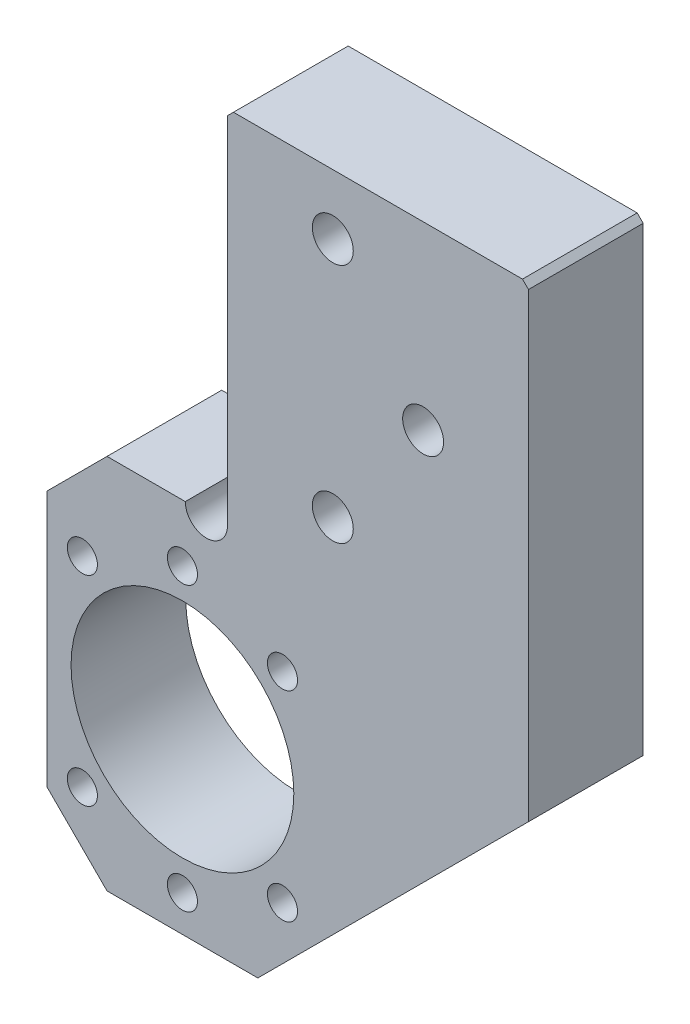
SolidWorks part; units mm, degrees
material "6061-T6 (SS)"
ref_plane "Front Plane" through (0, 0, 0) normal (0, 0, 1) x (1, 0, 0)
ref_plane "Top Plane" through (0, 0, 0) normal (0, 1, 0) x (1, 0, 0)
ref_plane "Right Plane" through (0, 0, 0) normal (1, 0, 0) x (0, 0, -1)
sketch "Sketch1" plane through (0, 0, 0) normal (0, 0, 1) x (1, 0, 0)
  line L0 (0.475, 33) -> (-12.525, 33)
  line L1 (-12.525, 33) -> (-22.525, 23)
  line L2 (-22.525, 23) -> (-22.525, -19.5)
  line L3 (-22.525, -19.5) -> (-12.525, -29.5)
  line L4 (-12.525, -29.5) -> (12.525, -29.5)
  line L5 (12.525, -29.5) -> (57.475, 15.45)
  line L6 (57.475, 15.45) -> (57.475, 93)
  line L7 (57.475, 93) -> (7.475, 93)
  line L8 (7.475, 93) -> (7.475, 33)
  line L9 (0, -55) -> (0, 55) construction
  line L10 (-12.525, -29.5) -> (-12.525, 33) construction
  line L11 (-37.525, 48.0126) -> (-37.525, -16.6245) construction
  line L12 (24.975, 83) -> (39.975, 83) construction
  line L13 (24.975, 83) -> (24.975, 43) construction
  line L14 (24.975, 43) -> (39.975, 43) construction
  line L15 (39.975, 83) -> (39.975, 43) construction
  line L16 (0, -23.5) -> (16.617, -16.617) construction
  line L17 (16.617, -16.617) -> (23.5, 0) construction
  line L18 (23.5, 0) -> (16.617, 16.617) construction
  line L19 (16.617, 16.617) -> (0, 23.5) construction
  line L20 (0, 23.5) -> (-16.617, 16.617) construction
  line L21 (-16.617, 16.617) -> (-23.5, 0) construction
  line L22 (-23.5, 0) -> (-16.617, -16.617) construction
  line L23 (-16.617, -16.617) -> (0, -23.5) construction
  line L24 (-28, -16.6245) -> (-28, 36.2473) construction
  circle A0 centre (0, 0) radius 18.5
  arc A1 (7.475, 33) -> (0.475, 33) centre (3.975, 33) cw
  circle A2 centre (0, 0) radius 21.7112 construction
  point P14 (0, -29.5)
  point P21 (39.975, 63)
  point P22 (24.975, 83)
  point P24 (24.975, 43)
  dimension "D1" = 37
  dimension "D6" = 3.5
  dimension "D2" = 30
  dimension "D3" = 6
  dimension "D4" = 33
  dimension "D5" = 10
  dimension "D7" = 7.475
  dimension "D8" = 17.5
  dimension "D9" = 10
  dimension "D10" = 17.5
  dimension "D11" = 15
  dimension "D12" = 10
  dimension "D13" = 40
  dimension "D14" = 47
  dimension "D15" = 9.525
  dimension "D16" = 28
  dimension "D17" = 45
extrude "Boss-Extrude1" add sketch "Sketch1" along normal mid plane 19.05
hole_wizard "M8x1.25 Tapped Hole1" positions "Sketch2" profile "Sketch3" tap size "M8x1.25" standard "ANSI Metric" end condition up to next
sketch "Sketch2" plane through (0, 0, 9.525) normal (0, 0, 1) x (1, 0, 0)
  line L0 (39.975, 83) -> (39.975, 43) construction
  point P0 (24.975, 43)
  point P3 (39.975, 63)
  point P7 (24.975, 83)
sketch "Sketch3" plane through (24.975, 43, 9.525) normal (1, 0, 0) x (0, -1, 0)
  line L0 (0, 0) -> (0, 19.05)
  line L1 (0, 19.05) -> (3.4, 19.05)
  line L2 (3.4, 19.05) -> (3.4, 0)
  line L5 (3.4, 0) -> (0, 0)
  line L11 (0, -6.35) -> (0, 107.95) construction
  dimension "Thru Tap Drill Dia." = 6.8
  dimension "Thru Tap Drill Depth" = 19.05
cosmetic thread "Hole Thread1" parameters "D2"=8
cosmetic thread "Hole Thread2" parameters "D2"=8
cosmetic thread "Hole Thread3" parameters "D2"=8
hole_wizard " Tapped Hole0" positions "Sketch4" profile "Sketch5" tap size "M6x1.0" standard "ANSI Metric" end condition up to next
sketch "Sketch4" plane through (0, 0, 9.525) normal (0, 0, 1) x (1, 0, 0)
  point P0 (0, 23.5)
  point P3 (-16.617, 16.617)
  point P6 (16.617, 16.617)
  point P9 (16.617, -16.617)
  point P12 (0, -23.5)
  point P15 (-16.617, -16.617)
sketch "Sketch5" plane through (0, 23.5, 9.525) normal (1, 0, 0) x (0, -1, 0)
  line L0 (0, 0) -> (0, 19.05)
  line L1 (0, 19.05) -> (2.5, 19.05)
  line L2 (2.5, 19.05) -> (2.5, 0)
  line L5 (2.5, 0) -> (0, 0)
  line L11 (0, -6.35) -> (0, 107.95) construction
  dimension "Thru Tap Drill Dia." = 5
  dimension "Thru Tap Drill Depth" = 19.05
cosmetic thread "Hole Thread4" parameters "D2"=6
cosmetic thread "Hole Thread5" parameters "D2"=6
cosmetic thread "Hole Thread6" parameters "D2"=6
cosmetic thread "Hole Thread7" parameters "D2"=6
cosmetic thread "Hole Thread8" parameters "D2"=6
cosmetic thread "Hole Thread9" parameters "D2"=6
chamfer "Chamfer1" distance 1 2 edges at (7.475, 93, 0) (57.475, 93, 0)
